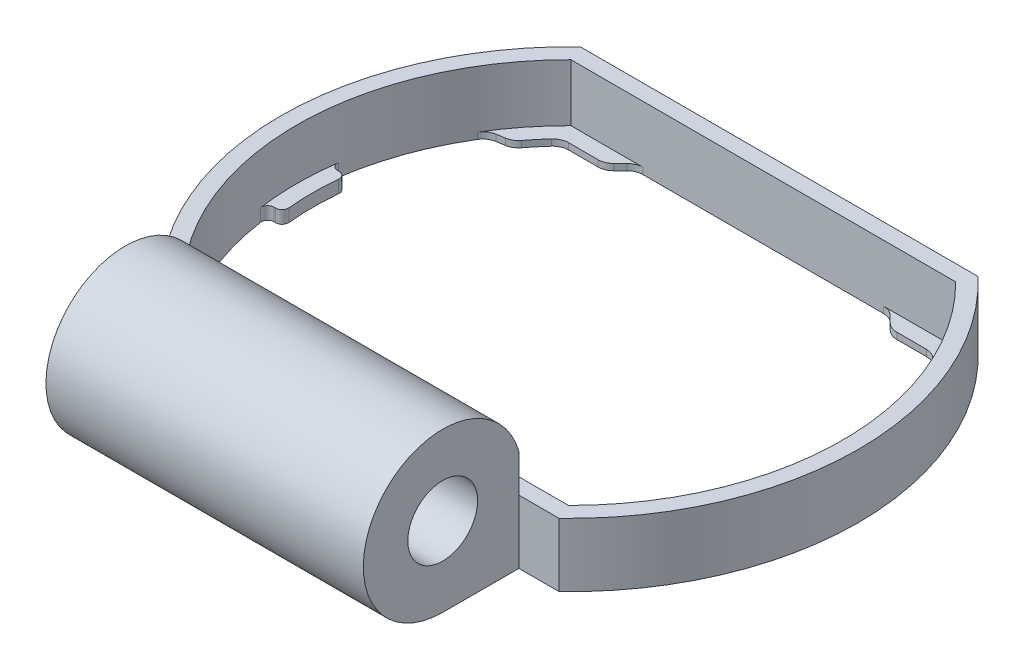
SolidWorks part; units mm, degrees
ref_plane "前视基准面" through (0, 0, 0) normal (0, 0, 1) x (1, 0, 0)
ref_plane "上视基准面" through (0, 0, 0) normal (0, 1, 0) x (1, 0, 0)
ref_plane "右视基准面" through (0, 0, 0) normal (1, 0, 0) x (0, 0, -1)
other "Configuration Table"
sketch "草图1" plane through (0, 0, 0) normal (0, 1, 0) x (1, 0, 0)
  line L0 (-12.1244, 12.2) -> (12.1244, 12.2)
  line L1 (-12.1244, -12.2) -> (12.1244, -12.2)
  line L2 (-12.1244, 12.2) -> (-12.1244, -12.2) construction
  line L3 (-12.53, 13.2) -> (12.53, 13.2)
  line L4 (-12.53, -13.2) -> (12.53, -13.2)
  arc A0 (-12.1244, 12.2) -> (-12.1244, -12.2) centre (0, 0) ccw
  arc A1 (12.1244, -12.2) -> (12.1244, 12.2) centre (0, 0) ccw
  arc A2 (12.53, -13.2) -> (12.53, 13.2) centre (0, 0) ccw
  arc A3 (-12.53, 13.2) -> (-12.53, -13.2) centre (0, 0) ccw
  dimension "D1" = 24.4
  dimension "D2" = 34.4
  dimension "D3" = 1
extrude "凸台-拉伸1" add sketch "草图1" along normal blind 4
sketch "草图2" plane through (0, 0, 0) normal (0, -1, 0) x (1, 0, 0)
  line L0 (12.1244, -12.2) -> (-12.1244, -12.2) construction
  line L1 (-12.1244, 12.2) -> (12.1244, 12.2) construction
  line L2 (12.1244, -12.2) -> (9, -12.2)
  line L3 (-12.1244, 12.2) -> (-9, 12.2)
  line L4 (-11.7047, 11.2) -> (-9, 11.2)
  line L5 (11.7047, -11.2) -> (9, -11.2)
  line L6 (-9, 12.2) -> (-9, 11.2)
  line L7 (-13.9151, 10.1099) -> (-13.1061, 9.5221)
  line L8 (-11.7047, 11.2) -> (11.7047, 11.2) construction
  line L9 (-12.1244, 12.2) -> (12.1244, 12.2) construction
  line L10 (12.1244, -12.2) -> (9, -12.2)
  line L11 (9, -12.2) -> (9, -11.2)
  line L12 (11.7047, -11.2) -> (9, -11.2)
  line L13 (13.9151, -10.1099) -> (13.1061, -9.5221)
  line L14 (11.7047, -11.2) -> (-11.7047, -11.2) construction
  line L15 (12.1244, -12.2) -> (-12.1244, -12.2) construction
  line L16 (0, 0) -> (0, 12.2) construction
  line L17 (-13.9151, -10.1099) -> (-13.1061, -9.5221)
  line L18 (-11.7047, -11.2) -> (-9, -11.2)
  line L19 (-9, -12.2) -> (-9, -11.2)
  line L20 (-12.1244, -12.2) -> (-9, -12.2)
  line L21 (-11.7047, -11.2) -> (-9, -11.2)
  line L22 (-12.1244, -12.2) -> (-9, -12.2)
  line L23 (13.9151, 10.1099) -> (13.1061, 9.5221)
  line L24 (9, 12.2) -> (9, 11.2)
  line L25 (11.7047, 11.2) -> (9, 11.2)
  line L26 (12.1244, 12.2) -> (9, 12.2)
  arc A0 (12.1244, -12.2) -> (12.1244, 12.2) centre (0, 0) ccw construction
  arc A1 (-12.1244, 12.2) -> (-12.1244, -12.2) centre (0, 0) ccw construction
  arc A2 (12.1244, -12.2) -> (13.9151, -10.1099) centre (0, 0) ccw
  arc A3 (-12.1244, 12.2) -> (-13.9151, 10.1099) centre (0, 0) ccw
  arc A4 (11.7047, -11.2) -> (13.1061, -9.5221) centre (0, 0) ccw
  arc A5 (-11.7047, 11.2) -> (-13.1061, 9.5221) centre (0, 0) ccw
  arc A6 (-12.1244, 12.2) -> (-12.1244, -12.2) centre (0, 0) ccw construction
  arc A7 (-11.7047, 11.2) -> (-11.7047, -11.2) centre (0, 0) ccw construction
  arc A8 (11.7047, -11.2) -> (13.1061, -9.5221) centre (0, 0) ccw
  arc A9 (12.1244, -12.2) -> (13.9151, -10.1099) centre (0, 0) ccw
  arc A10 (12.1244, -12.2) -> (12.1244, 12.2) centre (0, 0) ccw construction
  arc A11 (11.7047, -11.2) -> (11.7047, 11.2) centre (0, 0) ccw construction
  arc A12 (-12.1244, -12.2) -> (-13.9151, -10.1099) centre (0, 0) cw
  arc A13 (-11.7047, -11.2) -> (-13.1061, -9.5221) centre (0, 0) cw
  arc A14 (-11.7047, -11.2) -> (-13.1061, -9.5221) centre (0, 0) cw
  arc A15 (-12.1244, -12.2) -> (-13.9151, -10.1099) centre (0, 0) cw
  arc A16 (11.7047, 11.2) -> (13.1061, 9.5221) centre (0, 0) cw
  arc A17 (12.1244, 12.2) -> (13.9151, 10.1099) centre (0, 0) cw
  point P24 (0, 0)
  arc M18 (-12.1244, -12.2) -> (-12.1244, 12.2) centre (0, 0) cw
  line M19 (-12.1244, 12.2) -> (12.1244, 12.2)
  arc M20 (12.1244, 12.2) -> (12.1244, -12.2) centre (0, 0) cw
  line M21 (12.1244, -12.2) -> (-12.1244, -12.2)
  dimension "D2" = 9
  dimension "D3" = 36
  dimension "D5" = 9
  dimension "D1" = 1
  dimension "D4" = 2
extrude "凸台-拉伸2" add sketch "草图2" against normal blind 0.4 contours L18 A13 L17 L19 M18 M21 | A4 L5 L11 L13 M21 M20 | L25 A16 L23 L24 M20 M19 | A5 L4 L6 L7 M19 M18 region at (11.5099, 0, -11.2905) region at (-11.5099, 0, -11.2905) region at (11.5099, 0, 11.2905) region at (-11.5099, 0, 11.2905)
chamfer "倒角1" distance 1 angle 45 8 edges at (9, 0.2, -12.2) (13.9151, 0.2, -10.1099) (13.9151, 0.2, 10.1099) (9, 0.2, 12.2) (-9, 0.2, 12.2) (-13.9151, 0.2, 10.1099) (-13.9151, 0.2, -10.1099) (-9, 0.2, -12.2)
fillet "圆角1" radius 1 20 edges at (9, 0.2, -11.2) (8, 0.2, -12.2) (14.4644, 0.2, -9.307) (13.1061, 0.2, -9.5221) (11.7047, 0.2, -11.2) (14.4644, 0.2, 9.307) (13.1061, 0.2, 9.5221) (11.7047, 0.2, 11.2) (9, 0.2, 11.2) (8, 0.2, 12.2) (-8, 0.2, 12.2) (-9, 0.2, 11.2) (-11.7047, 0.2, 11.2) (-13.1061, 0.2, 9.5221) (-14.4644, 0.2, 9.307) (-8, 0.2, -12.2) (-9, 0.2, -11.2) (-13.1061, 0.2, -9.5221) (-14.4644, 0.2, -9.307) (-11.7047, 0.2, -11.2)
sketch "草图3" plane through (0, 0, 0) normal (1, 0, 0) x (0, 0, -1)
  line L0 (-13.2, 0) -> (13.2, 0) construction
  line L1 (-18, 0) -> (-13.2, 0)
  line L2 (-13.2, 0) -> (-13.2, 4)
  line L3 (-13.2, 4) -> (-13.2, 0) construction
  line L4 (-13.2, 4) -> (-13.2, 6.4)
  circle A0 centre (-18, 5) radius 2.2
  arc A1 (-13.2, 6.4) -> (-18, 0) centre (-18, 5) ccw
  point P5 (0, 0)
  dimension "D1" = 4.4
  dimension "D3" = 5
  dimension "D2" = 18
extrude "凸台-拉伸3" add sketch "草图3" along normal blind 10 and the other way blind 10
sketch "草图4" plane through (0, 0, 0) normal (0, -1, 0) x (1, 0, 0)
  line L0 (16.0761, 2) -> (17.0833, 2)
  line L1 (16.0761, -2) -> (17.0833, -2)
  line L2 (16.2, 0) -> (0, 0) construction
  line L3 (0, 0) -> (0, 12.2) construction
  line L4 (-7.5858, 12.2) -> (7.5858, 12.2) construction
  line L5 (-16.0761, 2) -> (-17.0833, 2)
  line L6 (-16.0761, -2) -> (-17.0833, -2)
  arc A0 (17.0833, 2) -> (17.0833, -2) centre (0, 0) cw
  arc A1 (14.7132, -8.9085) -> (14.7132, 8.9085) centre (0, 0) ccw construction
  arc A2 (16.0761, -2) -> (16.0761, 2) centre (0, 0) ccw
  arc A3 (-16.0761, -2) -> (-16.0761, 2) centre (0, 0) cw
  arc A4 (-17.0833, 2) -> (-17.0833, -2) centre (0, 0) ccw
  dimension "D1" = 1
  dimension "D2" = 4
extrude "凸台-拉伸4" add sketch "草图4" against normal blind 0.8
fillet "圆角2" radius 0.4 8 edges at (-16.0761, 0.4, 2) (-17.0833, 0.4, 2) (-16.0761, 0.4, -2) (-17.0833, 0.4, -2) (17.0833, 0.4, -2) (16.0761, 0.4, -2) (16.0761, 0.4, 2) (17.0833, 0.4, 2)
sketch "草图5" plane through (-10, 0, 0) normal (-1, 0, 0) x (0, 0, 1)
  line L0 (13.2, 2) -> (0, 2) construction
  line L1 (13.2, 4) -> (13.2, 0) construction
  line L2 (0, 2) -> (0, 0) construction
  line L3 (-13.2, 0) -> (13.2, 0) construction
  line L4 (18, 5) -> (0, 2) construction
  dimension "D1" = 18
  dimension "D2" = 3
